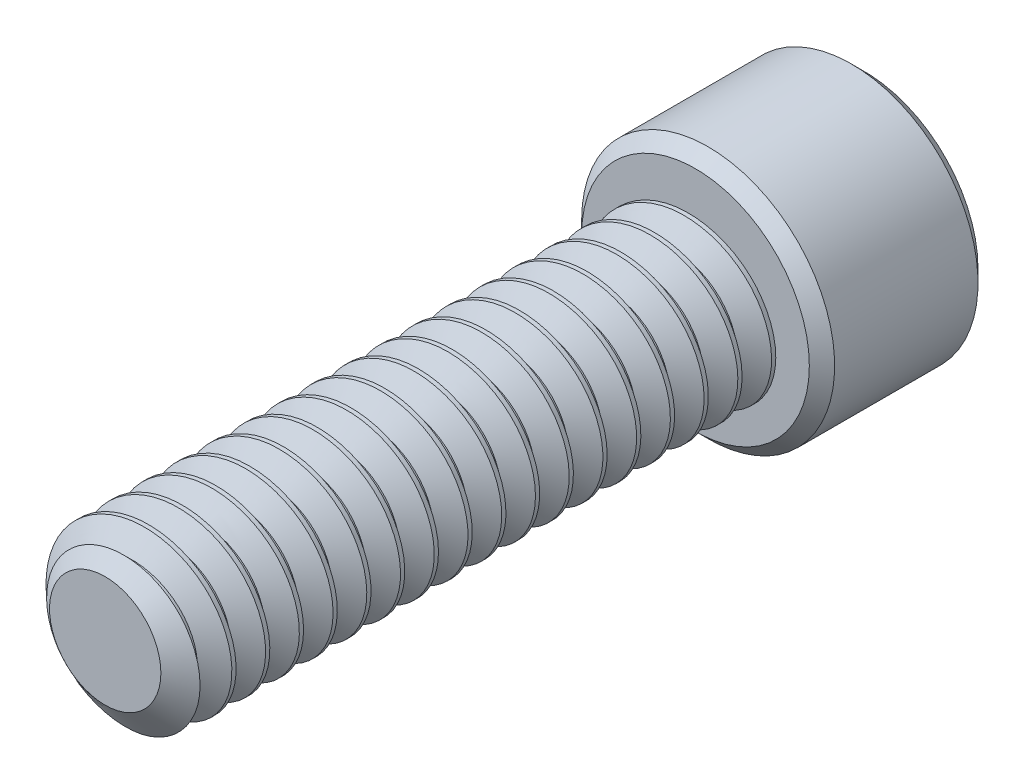
SolidWorks part; units mm, degrees
ref_plane "Front Plane" through (0, 0, 0) normal (0, 0, 1) x (1, 0, 0)
ref_plane "Top Plane" through (0, 0, 0) normal (0, 1, 0) x (1, 0, 0)
ref_plane "Right Plane" through (0, 0, 0) normal (1, 0, 0) x (0, 0, -1)
sketch "Sketch1" plane through (0, 0, 0) normal (0, 0, 1) x (1, 0, 0)
  circle A0 centre (0, 0) radius 3.175
  dimension "OD" = 6.35
extrude "Extrude1" add sketch "Sketch1" against normal blind 22.225
sketch "Sketch2" plane through (0, 0, 0) normal (0, 0, 1) x (1, 0, 0)
  circle A0 centre (0, 0) radius 3.175 construction
  circle A1 centre (0, 0) radius 3.175
curve "Helix/Spiral1" pitch 1.27 height 23.495 turns 18.5 parameters "pitch"=1.27
sketch "Sketch3" plane through (0, 0, 0) normal (1, 0, 0) x (0, 0, -1)
  line L0 (-1.1112, 3.175) -> (-0.635, 2.3501)
  line L1 (-0.635, 2.3501) -> (-0.4763, 2.3501)
  line L2 (-0.4763, 2.3501) -> (0, 3.175)
  line L3 (-1.1112, 3.175) -> (0, 3.175)
  line L4 (-0.5556, 3.175) -> (-0.5556, 2.3501) construction
  line L5 (-0.8731, 2.7626) -> (-0.2381, 2.7626) construction
  line L6 (0, 3.175) -> (0, -3.175) construction
  dimension "D1" = 0.1588
  dimension "D2" = 0.635
  dimension "D3" = 60
sweep "Cut-Sweep1" cut profiles "Sketch3" path "Helix/Spiral1"
sketch "Sketch4" plane through (0, 0, 0) normal (1, 0, 0) x (0, 0, -1)
  line L0 (0.7554, 3.175) -> (0, 2.0961)
  line L1 (0, 2.0961) -> (0, 3.175)
  line L2 (0.7554, 3.175) -> (0, 3.175)
  line L3 (-1.1112, 3.175) -> (0, 3.175) construction
  line L4 (0, 0) -> (7.0209, 0) construction
  dimension "D1" = 55
  dimension "D2" = 0.254
revolve "Cut-Revolve1" cut sketch "Sketch4" angle 360 about L4
sketch "Sketch5" plane through (0, 0, 0) normal (1, 0, 0) x (0, 0, -1)
  line L0 (22.225, -2.2654) -> (22.225, 2.3728) construction
  line L1 (22.225, 3.302) -> (87.4327, 3.302)
  line L2 (22.225, 3.302) -> (22.225, 0)
  line L3 (22.225, 0) -> (87.3125, 0)
  line L4 (87.3125, 2.9718) -> (87.3125, 0)
  line L5 (87.4327, 3.302) -> (87.3125, 2.9718)
  line L6 (0, 0) -> (9.9695, 0) construction
  point P3 (87.3125, 3.302)
  point P10 (87.3125, 3.302)
  dimension "D1" = 0.3302
  dimension "Thread min" = 87.3125
  dimension "D2" = 0.127
  dimension "D3" = 20
revolve "partially thread" [suppressed] add sketch "Sketch5" angle 360 about L6
sketch "Sketch6" plane through (0, 0, -22.225) normal (0, 0, -1) x (-1, 0, 0)
  circle A0 centre (0, 0) radius 4.7625
  dimension "head dia" = 9.525
extrude "Extrude2" add sketch "Sketch6" along normal blind 6.35
sketch "Sketch7" plane through (0, 0, -28.575) normal (0, 0, -1) x (-1, 0, 0)
  line L1 (0, 2.7496) -> (-2.3813, 1.3748)
  line L2 (-2.3813, 1.3748) -> (-2.3813, -1.3748)
  line L3 (-2.3813, -1.3748) -> (0, -2.7496)
  line L4 (0, -2.7496) -> (2.3813, -1.3748)
  line L5 (2.3813, -1.3748) -> (2.3813, 1.3748)
  line L6 (2.3813, 1.3748) -> (0, 2.7496)
  circle A0 centre (0, 0) radius 2.3813 construction
  dimension "hex dia" = 4.7625
extrude "Cut-Extrude1" cut sketch "Sketch7" against normal blind 3.5719
sketch "Sketch8" plane through (0, 0, -28.575) normal (0, 0, -1) x (-1, 0, 0)
  circle A0 centre (0, 0) radius 2.7496
extrude "Cut-Extrude2" cut sketch "Sketch8" against normal through all draft 45
chamfer "Chamfer1" distance 0.4763 angle 45 2 edges at (-4.7625, 0, -28.575) (-4.7625, 0, -22.225)
sketch "Sketch9" plane through (0, 0, 0) normal (1, 0, 0) x (0, 0, -1)
  line L0 (0, 3.175) -> (0, -3.175) construction
  line L1 (6.985, 3.175) -> (6.985, -3.175) construction
  dimension "D1" = 6.985
equation "\"D3@Helix/Spiral1\" = \"screw length@Extrude1\"+\"pitch@Helix/Spiral1\""
equation "\"D1@Sketch3\" = \"pitch@Helix/Spiral1\"*.125"
equation "\"D2@Sketch3\" = \"pitch@Helix/Spiral1\"*.5"
equation "\"D1@Cut-Extrude1\" = \"hex dia@Sketch7\"*.75"
equation "\"D1@Chamfer1\" = \"head dia@Sketch6\"*.05"
equation "\"D1@Sketch9\" = \"pitch@Helix/Spiral1\"*5.5"
